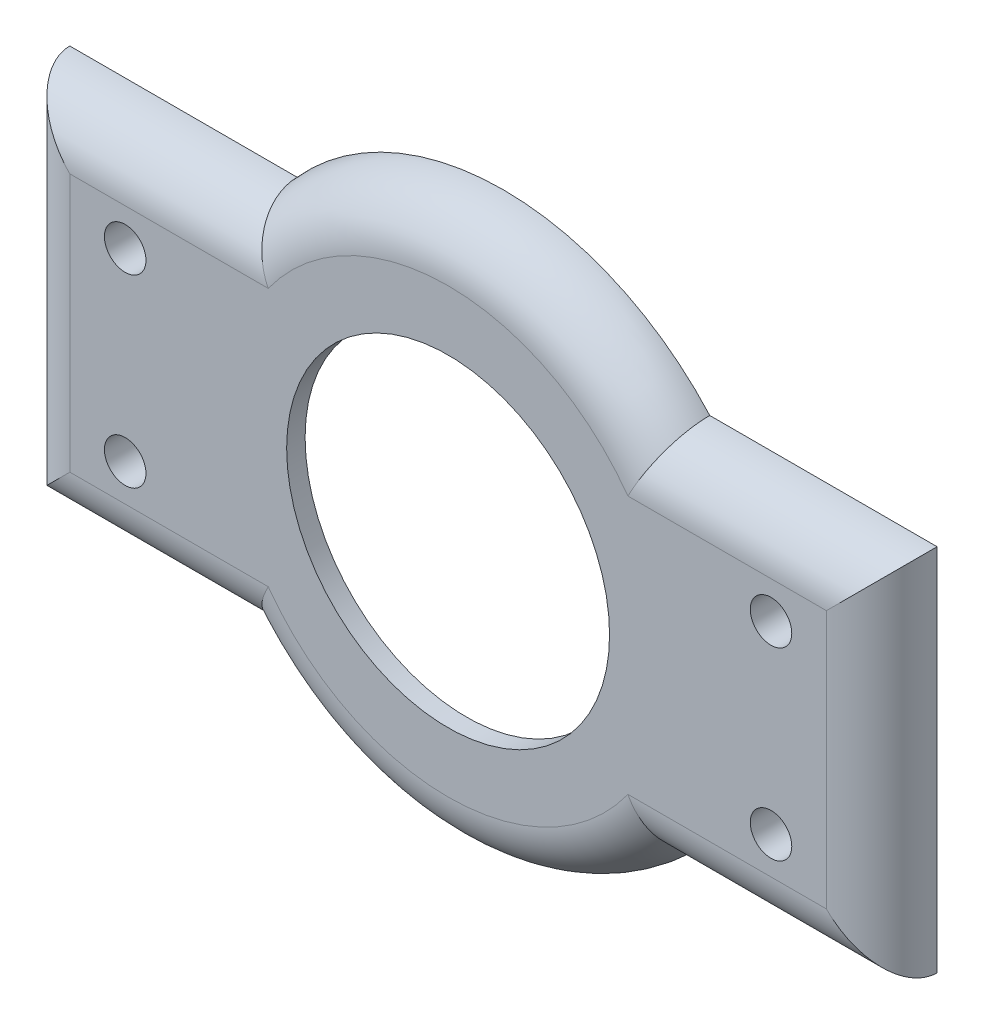
SolidWorks part; units mm, degrees
material "Nylon 6/10"
ref_plane "Front Plane" through (0, 0, 0) normal (0, 0, 1) x (1, 0, 0)
ref_plane "Top Plane" through (0, 0, 0) normal (0, 1, 0) x (1, 0, 0)
ref_plane "Right Plane" through (0, 0, 0) normal (1, 0, 0) x (0, 0, -1)
sketch "Sketch1" plane through (0, 0, 0) normal (0, 0, 1) x (1, 0, 0)
  circle A0 centre (0, 0) radius 30
  dimension "D1" = 60
extrude "Boss-Extrude1" add sketch "Sketch1" along normal blind 2
sketch "Sketch2" plane through (0, 0, 0) normal (0, 0, -1) x (-1, 0, 0)
  circle A0 centre (0, 0) radius 25
  circle A1 centre (0, 0) radius 30
  dimension "D1" = 50
  dimension "D2" = 60
extrude "Boss-Extrude2" add sketch "Sketch2" along normal blind 4
sketch "Sketch3" plane through (0, 0, -4) normal (0, 0, -1) x (-1, 0, 0)
  line L1 (-47, -20) -> (47, -20)
  line L2 (-47, -20) -> (-47, 20)
  line L3 (-47, 20) -> (47, 20)
  line L4 (47, -20) -> (47, 20)
  line L5 (-47, -20) -> (47, 20) construction
  line L6 (-47, 20) -> (47, -20) construction
  point P0 (0, 0)
  dimension "D1" = 40
  dimension "D2" = 47
extrude "Boss-Extrude3" add sketch "Sketch3" against normal up to surface (6 mm away) up to face at (30, 0, 2)
sketch "Sketch4" plane through (0, 0, -4) normal (0, 0, -1) x (-1, 0, 0)
  circle A0 centre (0, 0) radius 25
  dimension "D1" = 50
extrude "Cut-Extrude1" cut sketch "Sketch4" against normal up to surface (4 mm away) up to face at (0, 22.5, 0)
sketch "Sketch5" plane through (0, 0, 0) normal (0, 0, -1) x (-1, 0, 0)
  circle A0 centre (0, 0) radius 17.5
  dimension "D1" = 35
extrude "Cut-Extrude2" cut sketch "Sketch5" against normal through all
fillet "Fillet1" radius 6 8 edges at (47, 0, 2) (34.6803, -20, 2) (34.6803, 20, 2) (0, 30, 2) (0, -30, 2) (-34.6803, -20, 2) (-47, 0, 2) (-34.6803, 20, 2)
hole_wizard "M4 Clearance Hole1" positions "Sketch6" profile "Sketch7" hole size "M4" standard "ANSI Metric" end condition through all
sketch "Sketch6" plane through (0, 0, 2) normal (0, 0, 1) x (1, 0, 0)
  point P0 (-35, 10)
  point P2 (-35, -10)
  point P4 (35, 10)
  point P6 (35, -10)
  dimension "D1" = 35
  dimension "D2" = 35
  dimension "D3" = 10
  dimension "D4" = 10
sketch "Sketch7" plane through (-35, 10, 2) normal (1, 0, 0) x (0, -1, 0)
  line L0 (0, 0) -> (0, 6.3265)
  line L1 (0, 6.3265) -> (2.25, 6.3265)
  line L2 (2.25, 6.3265) -> (2.25, 0)
  line L5 (2.25, 0) -> (0, 0)
  line L11 (0, -6.35) -> (0, 107.95) construction
  dimension "Thru Hole Dia." = 4.5
  dimension "Thru Hole Depth" = 6.3265
